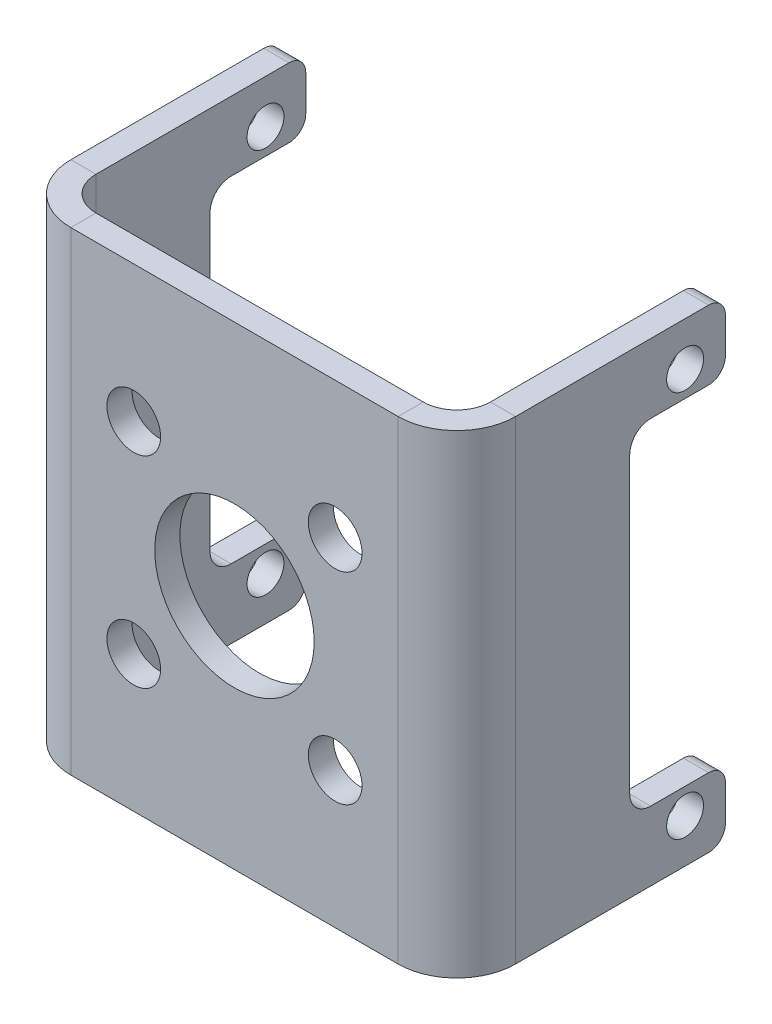
SolidWorks part; units mm, degrees
note: The reader was unsure of these and kept them because the rebuilt part matched: flange length of "Edge-Flange1".
ref_plane "Front Plane" through (0, 0, 0) normal (0, 0, 1) x (1, 0, 0)
ref_plane "Top Plane" through (0, 0, 0) normal (0, 1, 0) x (1, 0, 0)
ref_plane "Right Plane" through (0, 0, 0) normal (1, 0, 0) x (0, 0, -1)
sketch "Sketch1" plane through (0, 0, 0) normal (0, 0, 1) x (1, 0, 0)
  line L1 (11.75, -14.125) -> (-11.75, -14.125)
  line L2 (11.75, -14.125) -> (11.75, 14.125)
  line L3 (11.75, 14.125) -> (-11.75, 14.125)
  line L4 (-11.75, -14.125) -> (-11.75, 14.125)
  line L5 (11.75, -14.125) -> (-11.75, 14.125) construction
  line L6 (11.75, 14.125) -> (-11.75, -14.125) construction
  point P0 (0, 0)
  dimension "D1" = 23.5
  dimension "D2" = 28.25
base flange "Base-Flange1" sketch "Sketch1" thickness 1.5 reverse thickness direction no parameters "D1"=2
edge flange "Edge-Flange1" sketch "Sketch10" flange profiles "Sketch10", "Sketch11" flange angle 90 flange length 16 flange position material outside bend radius 2 thickness 1.5 relief rectangular parameters "D6"=10, "D8"=1
sketch "Sketch10" plane through (11.75, 0, -1.5) normal (1, 0, 0) x (0, -1, 0)
  line L0 (14.125, 0) -> (-14.125, 0) construction
  line L1 (14.125, 0) -> (-14.125, 0)
  line L2 (-14.125, 0) -> (-14.125, 14.5)
  line L3 (-14.125, 14.5) -> (14.125, 14.5)
  line L4 (14.125, 14.5) -> (14.125, 0)
sketch "Sketch11" plane through (-11.75, 0, -1.5) normal (-1, 0, 0) x (0, 1, 0)
  line L0 (14.125, 0) -> (-14.125, 0) construction
  line L1 (14.125, 0) -> (-14.125, 0)
  line L2 (-14.125, 0) -> (-14.125, 14.5)
  line L3 (-14.125, 14.5) -> (14.125, 14.5)
  line L4 (14.125, 14.5) -> (14.125, 0)
bend "EdgeBend1" bend radius 2 bend angle 90 parameters "D5"=1
bend "EdgeBend2" bend radius 2 bend angle 90 parameters "D5"=2
sketch "Sketch12" plane through (0, 0, 0) normal (0, 0, 1) x (1, 0, 0)
  line L1 (6, -6) -> (-6, -6) construction
  line L2 (6, -6) -> (6, 6) construction
  line L3 (6, 6) -> (-6, 6) construction
  line L4 (-6, -6) -> (-6, 6) construction
  line L5 (6, -6) -> (-6, 6) construction
  line L6 (6, 6) -> (-6, -6) construction
  circle A0 centre (-6, 6) radius 1.6
  circle A1 centre (6, 6) radius 1.6
  circle A2 centre (6, -6) radius 1.6
  circle A3 centre (-6, -6) radius 1.6
  circle A4 centre (0, 0) radius 4.75
  point P0 (0, 0)
  dimension "D1" = 3.2
  dimension "D3" = 9.5
  dimension "D2" = 12
extrude "Cut-Extrude1" cut sketch "Sketch12" against normal through all normal cut yes
sketch "Sketch13" plane through (13.25, 0, 0) normal (1, 0, 0) x (0, 0, -1)
  line L0 (39.95, 10) -> (10.3, 10)
  line L1 (10.3, 10) -> (10.3, -10)
  line L2 (10.3, -10) -> (39.95, -10)
  line L3 (39.95, -10) -> (39.95, 10)
  circle A0 centre (13.6, 11.525) radius 1.1
  circle A1 centre (13.6, -11.525) radius 1.1
  dimension "D1" = 2.2
extrude "Cut-Extrude2" cut sketch "Sketch13" against normal through all normal cut yes
fillet "Fillet1" radius 1.25 4 edges at (-12.5, 10, -10.3) (-12.5, -10, -10.3) (12.5, -10, -10.3) (12.5, 10, -10.3)
fillet "Fillet2" radius 1 8 edges at (12.5, -14.125, -16) (12.5, -10, -16) (12.5, 10, -16) (12.5, 14.125, -16) (-12.5, 10, -16) (-12.5, 14.125, -16) (-12.5, -14.125, -16) (-12.5, -10, -16)
sketch "Bend-Lines1" [suppressed] plane through (0, 0, 0) normal (0, 1, 0) x (1, 0, 0)
sketch "Bounding-Box1" [suppressed] plane through (0, 0, 0) normal (0, 1, 0) x (1, 0, 0)
sheet metal parameters "Sheet-Metal1" thickness 1.5 parameters "D1"=2
flat pattern "Flat-Pattern1" [suppressed]
sketch "Bend-Lines2" plane through (0, 0, 0) normal (0, 1, 0) x (1, 0, 0)
sketch3d "Bounding-Box2" [suppressed]
  line L0 (-11.75, 14.5, 0) -> (-11.75, -14.5, 0) construction
  line L1 (11.75, 14.5, 0) -> (11.75, -14.5, 0) construction
  line L2 (-11.75, 14.5, 0) -> (11.75, 14.5, 0) construction
  line L3 (-11.75, -14.5, 0) -> (11.75, -14.5, 0) construction
sheet metal parameters "Sheet-Metal2" thickness 1.5 parameters "D1"=2
flat pattern "Flat-Pattern1"
sketch "Bend-Lines2" plane through (0, 0, 0) normal (0, 0, 1) x (1, 0, 0)
  line L0 (-11.9098, 14.5) -> (-11.9098, -14.5) construction
  line L1 (11.9098, -14.5) -> (11.9098, 14.5) construction
  line L2 (-11.9098, 14.5) -> (-11.9098, -14.5) construction
  line L3 (11.9098, -14.5) -> (11.9098, 14.5) construction
sketch3d "Bounding-Box2" [suppressed]
  line L0 (-22.5697, -14.5, 0) -> (22.5697, -14.5, 0) construction
  line L1 (-22.5697, 14.5, 0) -> (22.5697, 14.5, 0) construction
  line L2 (-22.5697, -14.5, 0) -> (-22.5697, 14.5, 0) construction
  line L3 (22.5697, -14.5, 0) -> (22.5697, 14.5, 0) construction
bend of the flat pattern "EdgeBend1>1"
bend of the flat pattern "EdgeBend2>1"
sheet metal parameters "Sheet-Metal3" thickness 1.5 parameters "D1"=2
flat pattern "Flat-Pattern1"
sketch "Bend-Lines2" plane through (0, 0, 0) normal (0, 0, 1) x (1, 0, 0)
  line L0 (-11.9098, 13.75) -> (-11.9098, -13.75) construction
  line L1 (11.9098, -13.75) -> (11.9098, 13.75) construction
  line L2 (-11.9098, 13.75) -> (-11.9098, -13.75) construction
  line L3 (11.9098, -13.75) -> (11.9098, 13.75) construction
sketch3d "Bounding-Box2" [suppressed]
  line L0 (-25.5697, -13.75, 0) -> (25.5697, -13.75, 0) construction
  line L1 (-25.5697, 13.75, 0) -> (25.5697, 13.75, 0) construction
  line L2 (-25.5697, -13.75, 0) -> (-25.5697, 13.75, 0) construction
  line L3 (25.5697, -13.75, 0) -> (25.5697, 13.75, 0) construction
bend of the flat pattern "EdgeBend1>1"
bend of the flat pattern "EdgeBend2>1"
sheet metal parameters "Sheet-Metal4" thickness 1.5 parameters "D1"=2
flat pattern "Flat-Pattern1"
sketch "Bend-Lines2" plane through (0, 0, 0) normal (0, 0, 1) x (1, 0, 0)
  line L0 (-11.9098, 14.125) -> (-11.9098, -14.125) construction
  line L1 (11.9098, -14.125) -> (11.9098, 14.125) construction
  line L2 (-11.9098, 14.125) -> (-11.9098, -14.125) construction
  line L3 (11.9098, -14.125) -> (11.9098, 14.125) construction
sketch3d "Bounding-Box2" [suppressed]
  line L0 (-26.5697, -14.125, 0) -> (26.5697, -14.125, 0) construction
  line L1 (-26.5697, 14.125, 0) -> (26.5697, 14.125, 0) construction
  line L2 (-26.5697, -14.125, 0) -> (-26.5697, 14.125, 0) construction
  line L3 (26.5697, -14.125, 0) -> (26.5697, 14.125, 0) construction
bend of the flat pattern "EdgeBend1>1"
bend of the flat pattern "EdgeBend2>1"
